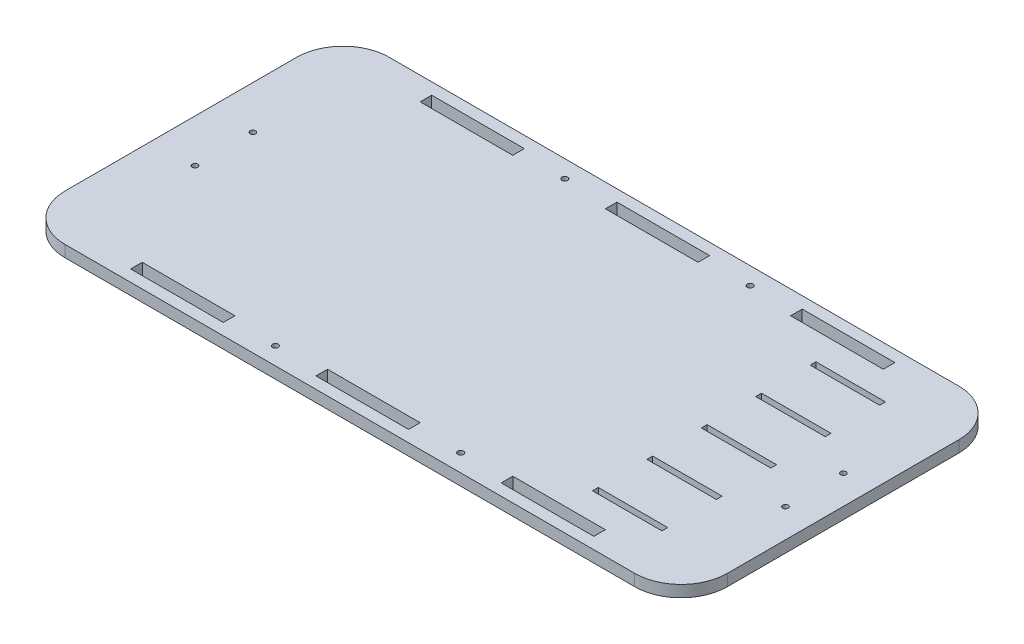
SolidWorks part; units mm, degrees
ref_plane "Front Plane" through (0, 0, 0) normal (0, 0, 1) x (1, 0, 0)
ref_plane "Top Plane" through (0, 0, 0) normal (0, 1, 0) x (1, 0, 0)
ref_plane "Right Plane" through (0, 0, 0) normal (1, 0, 0) x (0, 0, -1)
sketch "Sketch3" plane through (0, 0, 0) normal (0, 1, 0) x (1, 0, 0)
  line L1 (-156.21, -88.9) -> (156.21, -88.9)
  line L2 (-181.61, -63.5) -> (-181.61, 63.5)
  line L3 (-156.21, 88.9) -> (156.21, 88.9)
  line L4 (181.61, -63.5) -> (181.61, 63.5)
  line L5 (-181.61, -88.9) -> (181.61, 88.9) construction
  line L6 (-181.61, 88.9) -> (181.61, -88.9) construction
  arc A0 (156.21, -88.9) -> (181.61, -63.5) centre (156.21, -63.5) ccw
  arc A1 (156.21, 88.9) -> (181.61, 63.5) centre (156.21, 63.5) cw
  arc A2 (-156.21, -88.9) -> (-181.61, -63.5) centre (-156.21, -63.5) cw
  arc A3 (-181.61, 63.5) -> (-156.21, 88.9) centre (-156.21, 63.5) cw
  point P0 (0, 0)
  dimension "D3" = 25.4
  dimension "D1" = 177.8
  dimension "D2" = 363.22
extrude "BaseExtrude" add sketch "Sketch3" against normal blind 6.35
sketch "Sketch6" plane through (0, 0, 0) normal (0, 1, 0) x (1, 0, 0)
  line L0 (-181.61, 0) -> (181.61, 0) construction
  line L1 (-181.61, 63.5) -> (-181.61, -63.5) construction
  line L2 (181.61, -63.5) -> (181.61, 63.5) construction
  line L3 (0, -88.9) -> (0, 88.9) construction
  line L4 (-156.21, -88.9) -> (156.21, -88.9) construction
  line L5 (156.21, 88.9) -> (-156.21, 88.9) construction
  line L6 (3.937, 0) -> (3.937, 19.6413) construction
  circle A0 centre (-157.988, 15.875) radius 1.5
  circle A1 centre (-157.988, -15.875) radius 1.5
  circle A2 centre (165.862, -15.875) radius 1.5
  circle A3 centre (165.862, 15.875) radius 1.5
  dimension "D2" = 3
  dimension "D1" = 23.622
  dimension "D3" = 15.875
  dimension "D4" = 161.925
extrude "MainMountCut" cut sketch "Sketch6" against normal up to surface (6.35 mm away) up to face at (0, -6.35, 0)
sketch "Sketch7" plane through (0, 0, 0) normal (0, 1, 0) x (1, 0, 0)
  line L0 (76.6233, 79.375) -> (25.8233, 79.375) construction
  line L1 (127.4233, -82.55) -> (76.6233, -82.55)
  line L2 (127.4233, -82.55) -> (127.4233, -76.2)
  line L3 (127.4233, -76.2) -> (76.6233, -76.2)
  line L4 (76.6233, -82.55) -> (76.6233, -76.2)
  line L5 (25.8233, -82.55) -> (-24.9767, -82.55)
  line L6 (25.8233, -82.55) -> (25.8233, -76.2)
  line L7 (25.8233, -76.2) -> (-24.9767, -76.2)
  line L8 (-24.9767, -82.55) -> (-24.9767, -76.2)
  line L9 (-75.7767, -82.55) -> (-126.5767, -82.55)
  line L10 (-75.7767, -82.55) -> (-75.7767, -76.2)
  line L11 (-75.7767, -76.2) -> (-126.5767, -76.2)
  line L12 (-126.5767, -82.55) -> (-126.5767, -76.2)
  line L13 (127.4233, 76.2) -> (76.6233, 76.2)
  line L14 (127.4233, 76.2) -> (127.4233, 82.55)
  line L15 (127.4233, 82.55) -> (76.6233, 82.55)
  line L16 (76.6233, 76.2) -> (76.6233, 82.55)
  line L17 (25.8233, 76.2) -> (-24.9767, 76.2)
  line L18 (25.8233, 76.2) -> (25.8233, 82.55)
  line L19 (25.8233, 82.55) -> (-24.9767, 82.55)
  line L20 (-24.9767, 76.2) -> (-24.9767, 82.55)
  line L21 (-75.7767, 76.2) -> (-126.5767, 76.2)
  line L22 (-75.7767, 76.2) -> (-75.7767, 82.55)
  line L23 (-75.7767, 82.55) -> (-126.5767, 82.55)
  line L24 (-126.5767, 76.2) -> (-126.5767, 82.55)
  line L25 (-24.9767, 79.375) -> (-75.7767, 79.375) construction
  line L26 (-75.7767, -79.375) -> (-24.9767, -79.375) construction
  line L27 (76.6233, -79.375) -> (25.8233, -79.375) construction
  line L28 (181.61, -63.5) -> (181.61, 63.5) construction
  line L32 (-156.21, -88.9) -> (156.21, -88.9) construction
  line L35 (156.21, 88.9) -> (-156.21, 88.9) construction
  circle A0 centre (51.2233, 79.375) radius 1.6
  circle A1 centre (-50.3767, 79.375) radius 1.6
  circle A2 centre (-50.3767, -79.375) radius 1.6
  circle A3 centre (51.2233, -79.375) radius 1.6
  dimension "D5" = 3.2
  dimension "D1" = 50.8
  dimension "D2" = 6.35
  dimension "D3" = 6.35
  dimension "D4" = 6.35
  dimension "D6" = 54.1867
extrude "WallCut" cut sketch "Sketch7" against normal through all
sketch "Sketch8" plane through (0, 0, 0) normal (0, 1, 0) x (1, 0, 0)
  line L0 (124.46, -58.1025) -> (124.46, -31.4325) construction
  line L1 (143.51, -61.2775) -> (105.41, -61.2775)
  line L2 (143.51, -61.2775) -> (143.51, -58.1025)
  line L3 (143.51, -58.1025) -> (105.41, -58.1025)
  line L4 (105.41, -61.2775) -> (105.41, -58.1025)
  line L5 (143.51, -31.4325) -> (105.41, -31.4325)
  line L6 (143.51, -31.4325) -> (143.51, -28.2575)
  line L7 (143.51, -28.2575) -> (105.41, -28.2575)
  line L8 (105.41, -31.4325) -> (105.41, -28.2575)
  line L9 (143.51, -1.5875) -> (105.41, -1.5875)
  line L10 (143.51, -1.5875) -> (143.51, 1.5875)
  line L11 (143.51, 1.5875) -> (105.41, 1.5875)
  line L12 (105.41, -1.5875) -> (105.41, 1.5875)
  line L13 (143.51, 28.2575) -> (105.41, 28.2575)
  line L14 (143.51, 28.2575) -> (143.51, 31.4325)
  line L15 (143.51, 31.4325) -> (105.41, 31.4325)
  line L16 (105.41, 28.2575) -> (105.41, 31.4325)
  line L17 (143.51, 58.1025) -> (105.41, 58.1025)
  line L18 (143.51, 58.1025) -> (143.51, 61.2775)
  line L19 (143.51, 61.2775) -> (105.41, 61.2775)
  line L20 (105.41, 58.1025) -> (105.41, 61.2775)
  line L21 (124.46, -28.2575) -> (124.46, -1.5875) construction
  line L22 (124.46, -61.2775) -> (124.46, -76.2) construction
  line L23 (124.46, 1.5875) -> (124.46, 28.2575) construction
  line L24 (124.46, 31.4325) -> (124.46, 58.1025) construction
  line L25 (127.4233, -76.2) -> (76.6233, -76.2) construction
  line L26 (124.46, 61.2775) -> (124.46, 76.2) construction
  line L27 (76.6233, 76.2) -> (127.4233, 76.2) construction
  line L28 (181.61, -63.5) -> (181.61, 63.5) construction
  dimension "D1" = 3.175
  dimension "D2" = 26.67
  dimension "D3" = 38.1
  dimension "D4" = 57.15
extrude "WireMountCut" cut sketch "Sketch8" against normal through all
